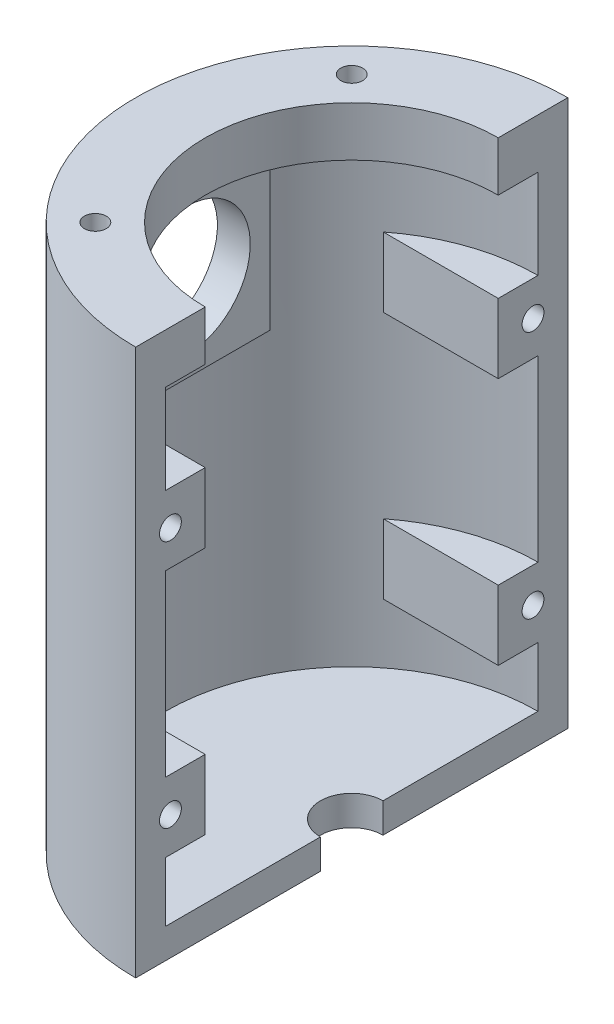
SolidWorks part; units mm, degrees
ref_plane "正面" through (0, 0, 0) normal (0, 0, 1) x (1, 0, 0)
ref_plane "平面" through (0, 0, 0) normal (0, 1, 0) x (1, 0, 0)
ref_plane "右側面" through (0, 0, 0) normal (1, 0, 0) x (0, 0, -1)
sketch "ｽｹｯﾁ1" plane through (0, 0, 0) normal (0, 1, 0) x (1, 0, 0)
  line L0 (0, -21.75) -> (0, -14.75)
  line L1 (0, -14.75) -> (0, 14.75) construction
  line L2 (0, 14.75) -> (0, 21.75)
  arc A0 (0, 21.75) -> (0, -21.75) centre (0, 0) ccw
  arc A1 (0, 14.75) -> (0, -14.75) centre (0, 0) ccw
  dimension "D1" = 14.75
  dimension "D2" = 7
extrude "ﾎﾞｽ - 押し出し1" add sketch "ｽｹｯﾁ1" along normal blind 55
sketch "ｽｹｯﾁ2" plane through (0, 55, 0) normal (0, 1, 0) x (1, 0, 0)
  circle A0 centre (0, 0) radius 14.75
  circle A1 centre (0, 0) radius 18.75
  arc A2 (0, 14.75) -> (0, -14.75) centre (0, 0) ccw construction
  arc A3 (0, 21.75) -> (0, -21.75) centre (0, 0) ccw construction
  dimension "D1" = 3
extrude "ｶｯﾄ - 押し出し1" cut sketch "ｽｹｯﾁ2" against normal through all from offset 5 offset against normal yes
sketch "ｽｹｯﾁ4" plane through (0, 0, 0) normal (1, 0, 0) x (0, 0, -1)
  line L0 (-14.75, 12.5) -> (-21.75, 12.5) construction
  line L1 (-21.75, 41) -> (-21.75, 34)
  line L2 (-18.75, 50) -> (-14.75, 50) construction
  line L3 (21.75, 55) -> (21.75, 0) construction
  line L4 (18.75, 50) -> (18.75, 0) construction
  line L5 (-21.75, 16) -> (-14.75, 16)
  line L6 (-14.75, 16) -> (-14.75, 9)
  line L7 (-14.75, 9) -> (-21.75, 9)
  line L8 (-21.75, 9) -> (-21.75, 16)
  line L9 (-21.75, 50) -> (21.75, 50) construction
  line L10 (0, 25) -> (-21.75, 25) construction
  line L11 (0, 25) -> (21.75, 25) construction
  line L12 (-21.75, 37.5) -> (21.75, 37.5) construction
  line L13 (-21.75, 0) -> (21.75, 0) construction
  line L14 (0, 50) -> (0, 0) construction
  line L15 (-18.25, 50) -> (-18.25, 0) construction
  line L16 (18.75, 50) -> (18.75, 37.5) construction
  line L17 (18.75, 37.5) -> (18.75, 25) construction
  line L18 (-21.75, 55) -> (-21.75, 0) construction
  line L19 (-21.75, 34) -> (-14.75, 34)
  line L20 (-14.75, 34) -> (-14.75, 41)
  line L21 (-14.75, 41) -> (-21.75, 41)
  line L22 (21.75, 9) -> (21.75, 16)
  line L23 (21.75, 16) -> (14.75, 16)
  line L24 (14.75, 16) -> (14.75, 9)
  line L25 (14.75, 9) -> (21.75, 9)
  line L26 (21.75, 34) -> (14.75, 34)
  line L27 (21.75, 41) -> (21.75, 34)
  line L28 (14.75, 41) -> (21.75, 41)
  line L29 (14.75, 34) -> (14.75, 41)
  circle A0 centre (-18.25, 37.5) radius 1.1 construction
  circle A1 centre (18.25, 37.5) radius 1.1 construction
  circle A2 centre (18.25, 12.5) radius 1.1 construction
  circle A3 centre (-18.25, 12.5) radius 1.1 construction
  dimension "D1" = 2.2
  dimension "D2" = 3.5
  dimension "D3" = 7
  dimension "D4" = 7
extrude "ﾎﾞｽ - 押し出し3" add sketch "ｽｹｯﾁ4" against normal up to next
sketch "ｽｹｯﾁ3" plane through (0, 0, 0) normal (1, 0, 0) x (0, 0, -1)
  line L0 (-21.75, 50) -> (21.75, 50) construction
  line L1 (0, 25) -> (-21.75, 25) construction
  line L2 (0, 25) -> (21.75, 25) construction
  line L3 (-21.75, 55) -> (-21.75, 0) construction
  line L4 (-21.75, 37.5) -> (21.75, 37.5) construction
  line L5 (21.75, 55) -> (21.75, 0) construction
  line L6 (-21.75, 0) -> (21.75, 0) construction
  line L7 (0, 50) -> (0, 0) construction
  line L8 (14.75, 50) -> (18.75, 50) construction
  line L9 (-18.25, 50) -> (-18.25, 0) construction
  line L10 (18.75, 50) -> (18.75, 37.5) construction
  line L11 (18.75, 37.5) -> (18.75, 25) construction
  line L12 (18.75, 50) -> (18.75, 41) construction
  circle A0 centre (-18.25, 37.5) radius 1.1
  circle A1 centre (18.25, 37.5) radius 1.1
  circle A2 centre (18.25, 12.5) radius 1.1
  circle A3 centre (-18.25, 12.5) radius 1.1
  dimension "D1" = 2.2
  dimension "D2" = 3.5
extrude "ｶｯﾄ - 押し出し2" cut sketch "ｽｹｯﾁ3" against normal blind 5
sketch "ｽｹｯﾁ5" plane through (0, 55, 0) normal (0, 1, 0) x (1, 0, 0)
  line L0 (0, 0) -> (-14.75, 0) construction
  line L1 (-14.75, 0) -> (-18.25, 0) construction
  line L2 (-18.25, 0) -> (-21.75, 0) construction
  line L3 (0, 0) -> (-12.9047, 12.9047) construction
  line L4 (-12.9047, -12.9047) -> (0, 0) construction
  circle A0 centre (0, 0) radius 18.25 construction
  arc A1 (0, 14.75) -> (0, -14.75) centre (0, 0) ccw construction
  arc A2 (0, 21.75) -> (0, -21.75) centre (0, 0) ccw construction
  circle A3 centre (-12.9047, -12.9047) radius 1.1
  circle A4 centre (-12.9047, 12.9047) radius 1.1
  dimension "D1" = 2.2
  dimension "D2" = 45
  dimension "D3" = 90
extrude "ｶｯﾄ - 押し出し3" cut sketch "ｽｹｯﾁ5" against normal up to vertex (5 mm away) up to point (0, 50, -14.75)
sketch "ｽｹｯﾁ6" plane through (0, 55, 0) normal (0, 1, 0) x (1, 0, 0)
  line L0 (-20.0203, 8.5) -> (-20.0203, -8.5)
  arc A0 (0, 21.75) -> (0, -21.75) centre (0, 0) ccw construction
  arc A1 (-20.0203, 8.5) -> (-20.0203, -8.5) centre (0, 0) ccw
  dimension "D1" = 17
extrude "ｶｯﾄ - 押し出し4" cut sketch "ｽｹｯﾁ6" against normal blind 17 from offset 5 offset against normal yes
sketch "ｽｹｯﾁ8" plane through (0, 50, 0) normal (0, -1, 0) x (1, 0, 0)
  line L0 (-16.7126, 8.5) -> (-16.7126, -8.5)
  arc A0 (-12.5377, -13.9417) -> (0, -18.75) centre (0, 0) ccw construction
  arc A1 (-16.7126, 8.5) -> (-16.7126, -8.5) centre (0, 0) ccw
  dimension "D1" = 17
extrude "ﾎﾞｽ - 押し出し4" add sketch "ｽｹｯﾁ8" along normal blind 17
sketch "ｽｹｯﾁ7" plane through (-20.0203, 0, 0) normal (-1, 0, 0) x (0, 0, 1)
  line L0 (8.5, 33) -> (-8.5, 50) construction
  line L2 (-8.5, 33) -> (8.5, 50) construction
  circle A0 centre (0, 41.5) radius 6.5
  dimension "D1" = 13
extrude "ｶｯﾄ - 押し出し5" cut sketch "ｽｹｯﾁ7" against normal through all
sketch "ｽｹｯﾁ9" plane through (0, 0, 0) normal (0, -1, 0) x (1, 0, 0)
  line L0 (0, 21.75) -> (0, 18.75) construction
  line L1 (0, -18.75) -> (0, -21.75) construction
  line L2 (0, 18.75) -> (0, -18.75) construction
  line L3 (0, 18.75) -> (0, 3.15)
  line L4 (0, -3.15) -> (0, -18.75)
  arc A0 (0, 18.75) -> (0, -18.75) centre (0, 0) ccw
  arc A1 (0, 18.75) -> (0, -18.75) centre (0, 0) ccw construction
  arc A2 (0, 3.15) -> (0, -3.15) centre (0, 0) ccw
  dimension "D1" = 3.15
extrude "ﾎﾞｽ - 押し出し5" add sketch "ｽｹｯﾁ9" against normal blind 3
